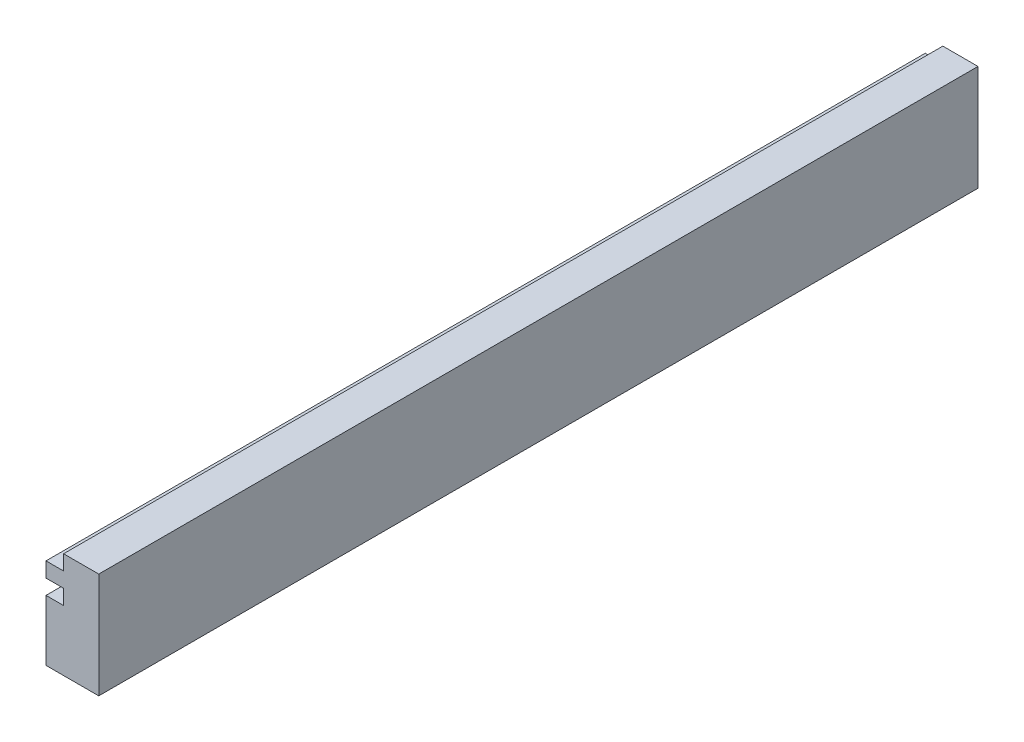
SolidWorks part; units mm, degrees
ref_plane "Front Plane" through (0, 0, 0) normal (0, 0, 1) x (1, 0, 0)
ref_plane "Top Plane" through (0, 0, 0) normal (0, 1, 0) x (1, 0, 0)
ref_plane "Right Plane" through (0, 0, 0) normal (1, 0, 0) x (0, 0, -1)
sketch "Sketch1" plane through (0, 0, 0) normal (0, 0, 1) x (1, 0, 0)
  line L1 (0, 0) -> (30, 0)
  line L2 (0, 0) -> (0, 60)
  line L3 (0, 60) -> (30, 60)
  line L4 (30, 0) -> (30, 60)
  dimension "D1" = 30
  dimension "D2" = 60
extrude "Boss-Extrude1" add sketch "Sketch1" along normal blind 500
sketch "Sketch2" plane through (0, 0, 500) normal (0, 0, 1) x (1, 0, 0)
  line L1 (0, 60) -> (10, 60)
  line L2 (0, 60) -> (0, 51.5)
  line L3 (0, 51.5) -> (10, 51.5)
  line L4 (10, 60) -> (10, 51.5)
  line L9 (0, 43) -> (0, 34.5)
  line L10 (0, 43) -> (10, 43)
  line L11 (10, 43) -> (10, 34.5)
  line L12 (0, 34.5) -> (10, 34.5)
  line M1 (0, 60) -> (0, 0)
  dimension "D1" = 10
  dimension "D2" = 8.5
  dimension "D3" = 2
  dimension "D4" = 8.5
extrude "Cut-Extrude1" cut sketch "Sketch2" against normal blind 500 contours L12 L11 L10 M1 | L2 L1 L4 L3 region at (5, 38.75, 500)
sketch "Sketch3" plane through (0, 0, 0) normal (0, 0, -1) x (-1, 0, 0)
  line L0 (0, 34.5) -> (0, 0) construction
  line L1 (0, 26) -> (-10, 26)
  line L2 (0, 26) -> (0, 17.5)
  line L3 (0, 17.5) -> (-10, 17.5)
  line L4 (-10, 26) -> (-10, 17.5)
  line L5 (0, 34.5) -> (-10, 34.5) construction
  dimension "D1" = 10
  dimension "D2" = 8.5
  dimension "D3" = 8.5
extrude "Cut-Extrude2" cut sketch "Sketch3" against normal blind 42.89
